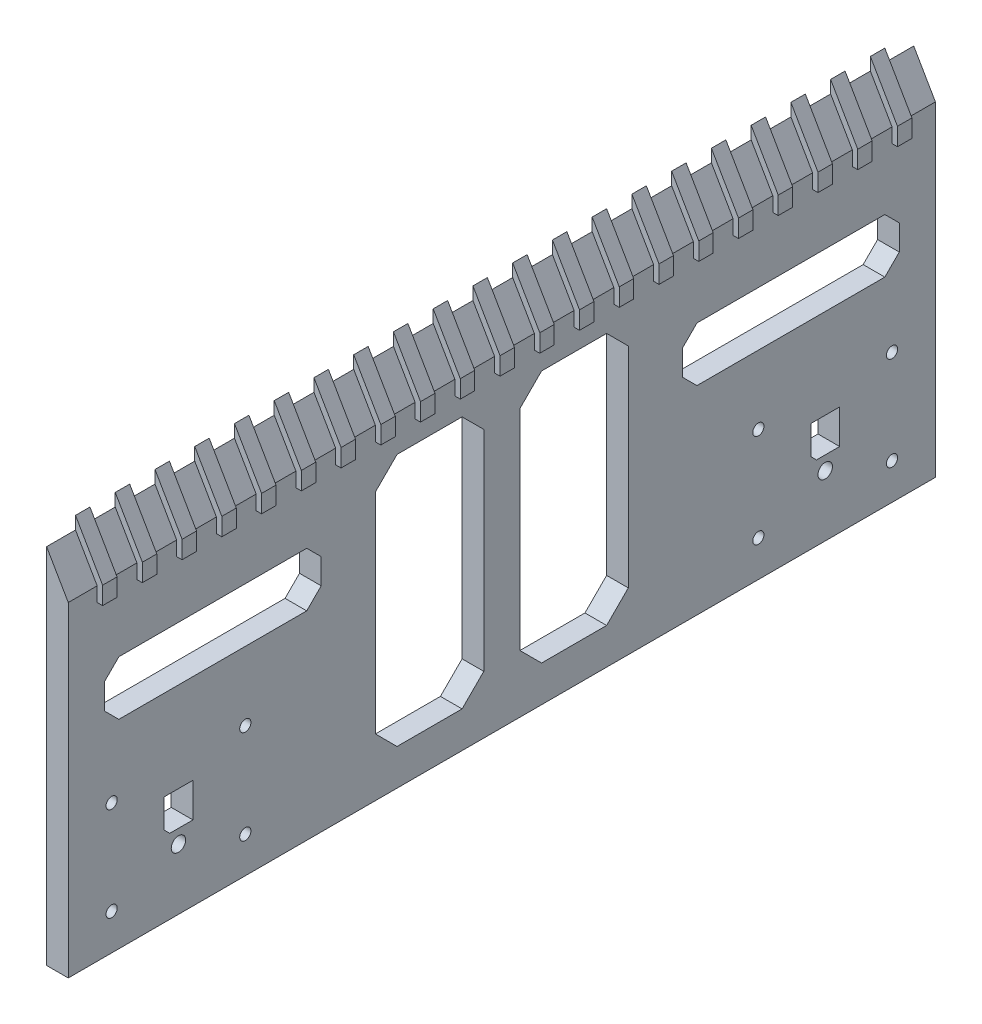
SolidWorks part; units mm, degrees
ref_plane "前视基准面" through (0, 0, 0) normal (0, 0, 1) x (1, 0, 0)
ref_plane "上视基准面" through (0, 0, 0) normal (0, 1, 0) x (1, 0, 0)
ref_plane "右视基准面" through (0, 0, 0) normal (1, 0, 0) x (0, 0, -1)
sketch "草图1" plane through (0, 0, 0) normal (1, 0, 0) x (0, 0, -1)
  line L1 (0, 0) -> (240, 0)
  line L2 (0, 0) -> (0, -90)
  line L3 (0, -90) -> (240, -90)
  line L4 (240, 0) -> (240, -90)
  dimension "D1" = 240
  dimension "D2" = 90
extrude "凸台-拉伸1" add sketch "草图1" along normal blind 6
sketch "草图2" plane through (6, 0, 0) normal (1, 0, 0) x (0, 0, -1)
  line L0 (0, 0) -> (0, -90) construction
  line L1 (12, -54) -> (49, -54) construction
  line L2 (12, -54) -> (12, -80) construction
  line L3 (12, -80) -> (49, -80) construction
  line L4 (49, -54) -> (49, -80) construction
  line L5 (240, 0) -> (0, 0) construction
  line L6 (120, 0) -> (120, -90) construction
  line L7 (0, -90) -> (240, -90) construction
  line L8 (191, -54) -> (191, -80) construction
  line L9 (228, -80) -> (191, -80) construction
  line L10 (228, -54) -> (228, -80) construction
  line L11 (228, -54) -> (191, -54) construction
  circle A0 centre (12, -54) radius 1.55
  circle A1 centre (49, -80) radius 1.55
  circle A2 centre (49, -54) radius 1.55
  circle A3 centre (12, -80) radius 1.55
  circle A4 centre (228, -80) radius 1.55
  circle A5 centre (191, -54) radius 1.55
  circle A6 centre (191, -80) radius 1.55
  circle A7 centre (228, -54) radius 1.55
  dimension "D5" = 3.1
  dimension "D1" = 12
  dimension "D2" = 54
  dimension "D3" = 37
  dimension "D4" = 26
extrude "切除-拉伸1" cut sketch "草图2" against normal through all
sketch "草图3" plane through (6, 0, 0) normal (1, 0, 0) x (0, 0, -1)
  line L0 (120, 0) -> (120, -90) construction
  line L1 (10, -20) -> (70, -20)
  line L2 (10, -20) -> (10, -35)
  line L3 (10, -35) -> (70, -35)
  line L4 (70, -20) -> (70, -35)
  line L5 (240, 0) -> (0, 0) construction
  line L6 (0, -90) -> (240, -90) construction
  line L7 (0, 0) -> (0, -90) construction
  line L8 (170, -20) -> (170, -35)
  line L9 (230, -35) -> (170, -35)
  line L10 (230, -20) -> (230, -35)
  line L11 (230, -20) -> (170, -20)
  dimension "D1" = 10
  dimension "D2" = 20
  dimension "D3" = 15
  dimension "D4" = 60
extrude "切除-拉伸2" cut sketch "草图3" against normal through all
sketch "草图4" plane through (6, 0, 0) normal (1, 0, 0) x (0, 0, -1)
  line L0 (120, 0) -> (120, -90) construction
  line L1 (85, -10) -> (115, -10)
  line L2 (85, -10) -> (85, -80)
  line L3 (85, -80) -> (115, -80)
  line L4 (115, -10) -> (115, -80)
  line L5 (240, 0) -> (0, 0) construction
  line L6 (0, -90) -> (240, -90) construction
  line L7 (0, 0) -> (0, -90) construction
  line L8 (125, -10) -> (125, -80)
  line L9 (155, -80) -> (125, -80)
  line L10 (155, -10) -> (155, -80)
  line L11 (155, -10) -> (125, -10)
  dimension "D1" = 10
  dimension "D2" = 70
  dimension "D3" = 85
  dimension "D4" = 30
extrude "切除-拉伸3" cut sketch "草图4" against normal through all contours L4 L1 L2 L3 | L8 L9 L10 L11 region at (6, -45, -100)
sketch "草图5" plane through (0, 0, 0) normal (-1, 0, 0) x (0, 0, 1)
  circle A0 centre (-191, -80) radius 3
  circle A1 centre (-228, -80) radius 3
  circle A2 centre (-191, -54) radius 3
  circle A3 centre (-228, -54) radius 3
  circle A4 centre (-49, -80) radius 3
  circle A5 centre (-12, -80) radius 3
  circle A6 centre (-12, -54) radius 3
  circle A7 centre (-49, -54) radius 3
  circle A8 centre (-49, -80) radius 1.55 construction
  point P11 (0, 0)
  dimension "D1" = 6
extrude "切除-拉伸4" cut sketch "草图5" against normal blind 3
sketch "草图6" plane through (0, 0, 0) normal (0, 0, 1) x (1, 0, 0)
  line L0 (6, 0) -> (0, 0)
  line L1 (0, 0) -> (0, 10.3923)
  line L2 (0, 10.3923) -> (6, 0)
  dimension "D1" = 30
extrude "凸台-拉伸2" add sketch "草图6" against normal blind 240
ref_plane "基准面1" through (0, 0, -120) normal (0, 0, 1) x (1, 0, 0)
chamfer "倒角1" distance 4 angle 45 8 edges at (3, -35, -170) (3, -35, -230) (3, -20, -230) (3, -20, -170) (3, -35, -70) (3, -20, -70) (3, -35, -10) (3, -20, -10)
chamfer "倒角2" distance 6 angle 45 8 edges at (3, -80, -125) (3, -10, -155) (3, -10, -125) (3, -80, -155) (3, -80, -115) (3, -80, -85) (3, -10, -115) (3, -10, -85)
sketch "草图8" plane through (0, 0, -120) normal (0, 0, 1) x (1, 0, 0)
  line L0 (0, 10.3923) -> (0, 13.8923)
  line L1 (0, 13.8923) -> (7.5, 0.9019)
  line L2 (7.5, 0.9019) -> (7.5, -4)
  line L3 (7.5, -4) -> (6, -4)
  line L4 (6, 0) -> (6, -90) construction
  line L5 (6, -4) -> (6, 0)
  line L6 (6, 0) -> (0, 10.3923) construction
  line L7 (6, 0) -> (0, 10.3923)
  dimension "D1" = 3.5
  dimension "D2" = 1.5
  dimension "D3" = 4
extrude "凸台-拉伸3" add sketch "草图8" along normal mid plane 4
pattern_linear "阵列(线性)1" count 11 spacing 11 along (0, 0, 1) count 11 spacing 11 along (0, 0, -1) of "凸台-拉伸3"
sketch "草图9" plane through (0, 0, 0) normal (-1, 0, 0) x (0, 0, 1)
  line L0 (-26.5, -67.77) -> (-26.5, -59.86)
  line L1 (-26.5, -59.86) -> (-34.5, -59.86)
  line L2 (-34.5, -59.86) -> (-34.5, -69.36)
  line L3 (-34.5, -69.36) -> (-28.09, -69.36)
  line L4 (0, 10.3923) -> (0, -90) construction
  line L5 (0, -90) -> (-240, -90) construction
  line L6 (-28.09, -69.36) -> (-26.5, -67.77)
  line L13 (-120, -24.7257) -> (-120, 24.7257) construction
  line L14 (-205.5, -59.86) -> (-205.5, -67.77)
  line L15 (-213.5, -59.86) -> (-205.5, -59.86)
  line L16 (-213.5, -59.86) -> (-213.5, -69.36)
  line L17 (-213.5, -69.36) -> (-207.09, -69.36)
  line L18 (-207.09, -69.36) -> (-205.5, -67.77)
  dimension "D1" = 26.5
  dimension "D2" = 20.64
  dimension "D3" = 8
  dimension "D4" = 9.5
  dimension "D6" = 45
  dimension "D7" = 45
extrude "切除-拉伸5" cut sketch "草图9" against normal blind 6
sketch "草图10" plane through (0, 0, 0) normal (-1, 0, 0) x (0, 0, 1)
  line L0 (0, -90) -> (-240, -90) construction
  line L1 (0, 10.3923) -> (0, -90) construction
  line L3 (-120, -24.7257) -> (-120, 24.7257) construction
  circle A0 centre (-30.5, -73.14) radius 2
  circle A2 centre (-209.5, -73.14) radius 2
  dimension "D1" = 16.86
  dimension "D2" = 30.5
extrude "切除-拉伸6" cut sketch "草图10" against normal blind 7
